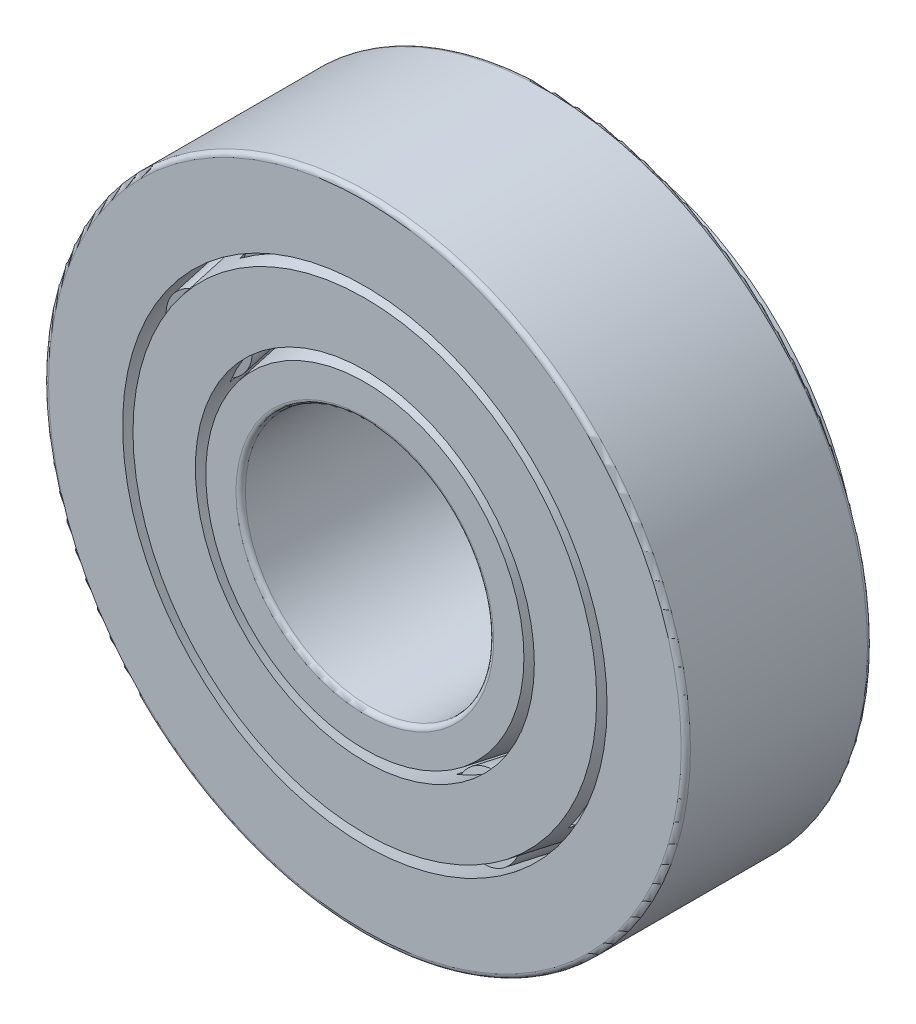
SolidWorks part; units mm, degrees
material "1060 Alloy"
ref_plane "Front Plane" through (0, 0, 0) normal (0, 0, 1) x (1, 0, 0)
ref_plane "Top Plane" through (0, 0, 0) normal (0, 1, 0) x (1, 0, 0)
ref_plane "Right Plane" through (0, 0, 0) normal (1, 0, 0) x (0, 0, -1)
sketch "Sketch1" plane through (0, 0, 0) normal (1, 0, 0) x (0, 0, -1)
  line L0 (-9.525, 0) -> (9.525, 0) construction
  line L1 (0, 0) -> (0, 24.6126) construction
  line L2 (-9.525, 9.525) -> (9.525, 9.525) construction
  line L3 (9.525, 9.525) -> (9.525, 15.56) construction
  line L4 (9.525, 15.56) -> (-9.525, 12.201) construction
  line L5 (-9.525, 12.201) -> (-9.525, 9.525) construction
  line L7 (-9.525, 24.6126) -> (4.7625, 24.6126)
  line L8 (4.7625, 24.6126) -> (4.7625, 21.0968)
  line L9 (4.7625, 21.0968) -> (-9.525, 18.5776)
  line L10 (-9.525, 18.5776) -> (-9.525, 24.6126)
  line L11 (-9.525, 18.5776) -> (-8.4345, 12.3933) construction
  line L12 (7.4185, 21.5652) -> (8.509, 15.3809) construction
  line L14 (-9.525, 12.201) -> (-8.4345, 12.3933) construction
  line L15 (-9.525, 12.201) -> (8.509, 15.3809) construction
  point P5 (0, 9.525)
  dimension "D1" = 100
  dimension "Width" = 19.05
  dimension "OD" = 49.2252
  dimension "Shaft Dia" = 19.05
  dimension "D2" = 15.0876
  dimension "D3" = 6.035
  dimension "Outer Wd" = 14.2875
  dimension "Bearing Wd" = 18.034
revolve "Revolve1" add sketch "Sketch1" angle 360 about L0
sketch "Sketch5" plane through (0, 0, 0) normal (1, 0, 0) x (0, 0, -1)
  line L0 (9.525, 15.56) -> (-9.525, 12.201) construction
  line L1 (9.525, 15.56) -> (-9.525, 12.201)
  line L2 (-9.525, 12.201) -> (-9.525, 9.525)
  line L3 (-9.525, 9.525) -> (9.525, 9.525)
  line L4 (9.525, 9.525) -> (9.525, 15.56)
revolve "Revolve4" add sketch "Sketch5" angle 360 about L0
sketch "Sketch2" plane through (0, 0, 0) normal (1, 0, 0) x (0, 0, -1)
  line L0 (-9.525, 17.7805) -> (-9.525, 12.9981)
  line L1 (4.7625, 20.2998) -> (7.5549, 20.7921)
  line L2 (-9.525, 12.9981) -> (4.7625, 15.5174)
  line L3 (7.4185, 21.5652) -> (8.509, 15.3809) construction
  line L4 (4.7625, 15.5174) -> (4.7625, 20.2998) construction
  line L5 (4.7625, 20.2998) -> (-9.525, 17.7805)
  line L6 (4.7625, 21.0968) -> (-9.525, 18.5776) construction
  line L7 (9.525, 15.56) -> (-9.525, 12.201) construction
  line L8 (-9.525, 18.5776) -> (4.7625, 21.0968) construction
  line L9 (-9.525, 12.201) -> (8.509, 15.3809) construction
  line L10 (7.5549, 20.7921) -> (8.3727, 16.1539)
  line L11 (-9.525, 18.5776) -> (-9.525, 17.7805) construction
  line L12 (-9.525, 12.9981) -> (-9.525, 12.201) construction
  line L13 (4.7625, 24.6126) -> (4.7625, 21.0968) construction
  line L14 (8.3727, 16.1539) -> (4.7625, 15.5174)
  dimension "D1" = 6.2797
  dimension "D2" = 4.7098
revolve "Revolve2" add sketch "Sketch2" angle 360 about L0
sketch "Sketch3" plane through (0, 0, 0) normal (1, 0, 0) x (0, 0, -1)
  line L0 (-9.525, 15.3893) -> (4.7625, 17.9086) construction
  line L1 (-9.525, 17.7805) -> (-9.525, 12.9981) construction
  line L2 (4.7625, 15.5174) -> (4.7625, 20.2998) construction
  line L3 (-7.8893, 15.6777) -> (-8.4345, 18.7698)
  line L5 (-8.4345, 18.7698) -> (4.2173, 21.0007)
  line L6 (4.2173, 21.0007) -> (4.7625, 17.9086)
  line L7 (4.7625, 17.9086) -> (-7.8893, 15.6777)
  line L8 (4.7625, 21.0968) -> (-9.525, 18.5776) construction
  line L9 (-9.525, 15.3893) -> (-8.9798, 15.4854) construction
  line L10 (-9.525, 18.5776) -> (-8.4345, 12.3933) construction
  line L11 (-8.9798, 15.4854) -> (-8.4345, 15.5816) construction
  line L12 (-8.4345, 15.5816) -> (-7.8893, 15.6777) construction
revolve "Cut-Revolve1" cut sketch "Sketch3" angle 360 about L0
sketch "Sketch4" plane through (0, 0, 0) normal (1, 0, 0) x (0, 0, -1)
  line L0 (-8.3904, 18.5197) -> (4.2614, 20.7506)
  line L1 (4.2614, 20.7506) -> (4.7625, 17.9086)
  line L2 (4.7625, 17.9086) -> (-7.8893, 15.6777)
  line L3 (-9.525, 15.3893) -> (-7.8893, 15.6777) construction
  line L4 (-7.8893, 15.6777) -> (-8.3904, 18.5197)
  line L6 (4.7625, 17.9086) -> (-7.8893, 15.6777) construction
  line L7 (4.7625, 21.0968) -> (-9.525, 18.5776) construction
  dimension "D1" = 0.254
revolve "Revolve3" add sketch "Sketch4" angle 360 about L0
ref_axis "Axis1" through (0, 0, -9.525) along (0, 0, 1)
pattern_circular "CirPattern1" count 12 every 30 about axis through (0, 0, -9.525) along (0, 0, 1) of "Cut-Revolve1"
pattern_circular "CirPattern2" count 12 every 30 about axis through (0, 0, -9.525) along (0, 0, 1) of bodies 403
fillet "Fillet1" radius 0.3572 2 edges at (24.6126, 0, -4.7625) (24.6126, 0, 9.525)
fillet "Fillet2" radius 0.3572 2 edges at (9.525, 0, -9.525) (9.525, 0, 9.525)
sketch "Sketch6" plane through (0, 0, 0) normal (1, 0, 0) x (0, 0, -1)
  line L0 (-49.2125, 24.6126) -> (-49.2125, 18.5776)
  line L1 (-49.2125, 18.5776) -> (-34.925, 21.0968)
  line L2 (-34.925, 21.0968) -> (-34.925, 24.6126)
  line L3 (-34.925, 24.6126) -> (-49.2125, 24.6126)
  line L4 (-9.525, 24.6126) -> (4.7625, 24.6126) construction
  line L5 (-9.525, 18.5776) -> (-9.525, 24.6126) construction
  line L6 (4.7625, 24.6126) -> (4.7625, 21.0968) construction
  line L8 (-9.525, 24.2554) -> (-9.525, -24.2554) construction
  dimension "D1" = 25.4
revolve "Revolve5" [suppressed] add sketch "Sketch6" angle 360 about L0
fillet "Fillet3" [suppressed] radius 0.3572
delete or keep bodies "Body-Delete1" [suppressed] type delete bodies bodies 399
equation "\"D3@Sketch1\" = \"D2@Sketch1\"/2.5"
equation "\"D2@Sketch2\" = \"D1@Sketch2\"*.75"
equation "\"Rollers@CirPattern2\" = \"OD@Sketch1\"*6"
equation "\"Angle@CirPattern2\" = 360/\"Rollers@CirPattern2\""
equation "\"D1@CirPattern1\" = \"Rollers@CirPattern2\""
equation "\"D2@CirPattern1\" = \"Angle@CirPattern2\""
equation "\"D1@Fillet1\" = \"Outer Wd@Sketch1\"*.025"
equation "\"D1@Fillet2\" = \"D1@Fillet1\""
equation "\"D1@Fillet3\" = \"D1@Fillet1\""
